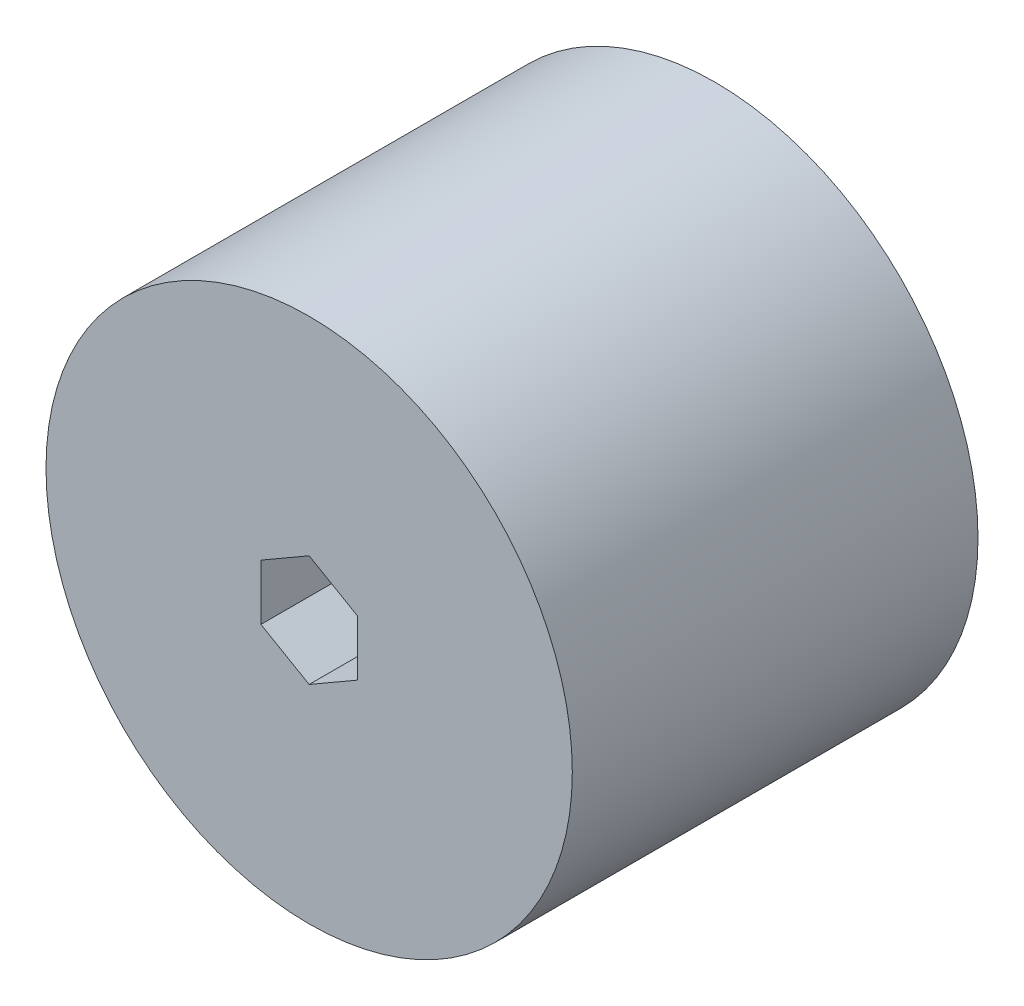
SolidWorks part; units mm, degrees
material "PET"
ref_plane "Front Plane" through (0, 0, 0) normal (0, 0, 1) x (1, 0, 0)
ref_plane "Top Plane" through (0, 0, 0) normal (0, 1, 0) x (1, 0, 0)
ref_plane "Right Plane" through (0, 0, 0) normal (1, 0, 0) x (0, 0, -1)
sketch "Sketch1" plane through (0, 0, 0) normal (0, 0, 1) x (1, 0, 0)
  line L1 (0, 8.0656) -> (-6.985, 4.0328)
  line L2 (-6.985, 4.0328) -> (-6.985, -4.0328)
  line L3 (-6.985, -4.0328) -> (0, -8.0656)
  line L4 (0, -8.0656) -> (6.985, -4.0328)
  line L5 (6.985, -4.0328) -> (6.985, 4.0328)
  line L6 (6.985, 4.0328) -> (0, 8.0656)
  circle A0 centre (0, 0) radius 38.1
  circle A1 centre (0, 0) radius 6.985 construction
  dimension "D1" = 76.2
  dimension "D2" = 13.97
extrude "Boss-Extrude1" add sketch "Sketch1" along normal blind 58.7375
